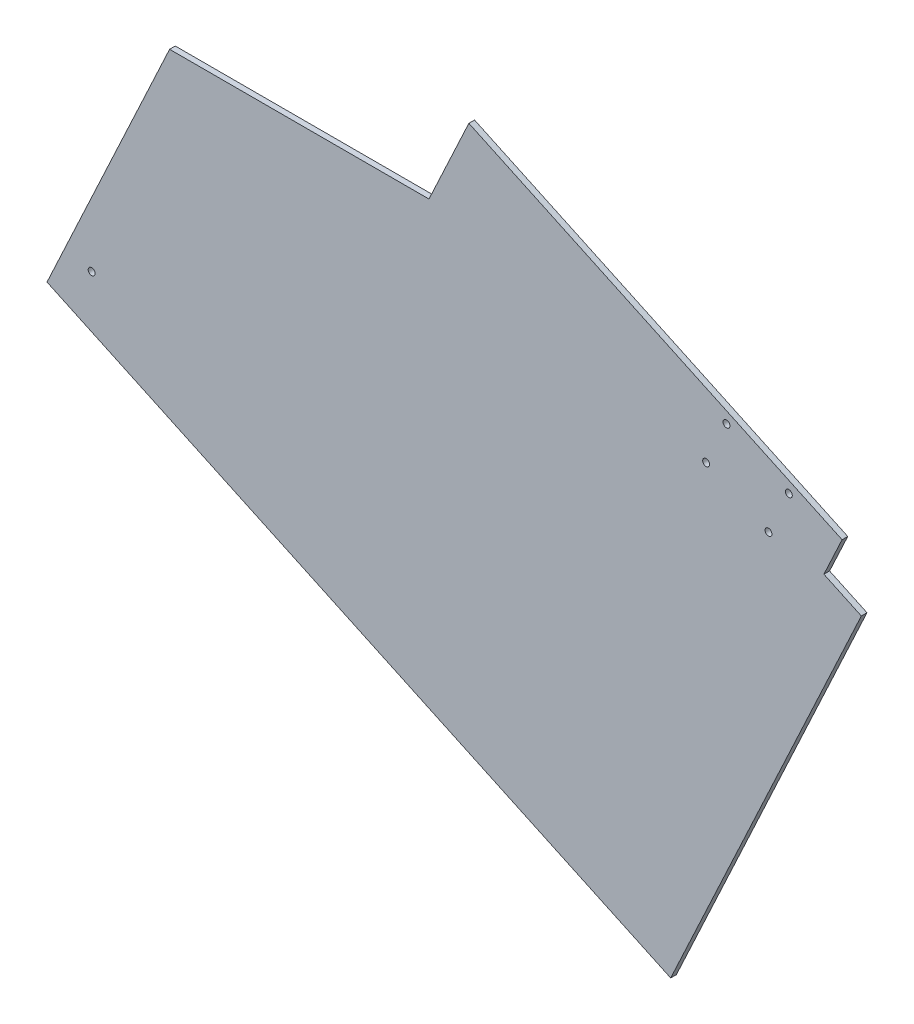
SolidWorks part; units mm, degrees
ref_plane "Front Plane" through (0, 0, 0) normal (0, 0, 1) x (1, 0, 0)
ref_plane "Top Plane" through (0, 0, 0) normal (0, 1, 0) x (1, 0, 0)
ref_plane "Right Plane" through (0, 0, 0) normal (1, 0, 0) x (0, 0, -1)
sketch "Sketch1" plane through (0, 0, 0) normal (0, 0, 1) x (1, 0, 0)
  line L0 (-261.1014, 0.0035) -> (-110.3324, 0.0035)
  line L1 (-110.3324, 0.0035) -> (-87.1479, 49.7228)
  line L2 (-87.1479, 49.7228) -> (129.7831, -51.4338)
  line L3 (129.7831, -51.4338) -> (119.2177, -74.0915)
  line L4 (119.2177, -74.0915) -> (140.969, -84.2344)
  line L5 (140.969, -84.2344) -> (30.1585, -321.8683)
  line L6 (30.1585, -321.8683) -> (-332.3646, -152.8209)
  line L7 (-332.3646, -152.8209) -> (-261.1014, 0.0035)
  line L8 (-257.4117, 0.0035) -> (-57.4117, 0.0035) construction
  line L9 (-332.3646, -152.8209) -> (-261.0998, 0.0069) construction
  line L10 (30.1585, -321.8683) -> (-332.3646, -152.8209) construction
  line L11 (140.969, -84.2344) -> (30.1585, -321.8683) construction
  line L12 (-189.2372, 97.3278) -> (129.7831, -51.4338) construction
  line L13 (119.2177, -74.0915) -> (140.969, -84.2344) construction
  line L14 (129.7831, -51.4338) -> (119.2177, -74.0915) construction
  line L15 (-110.3324, 0.0035) -> (-87.1479, 49.7228) construction
  circle A0 centre (87.0035, -69.0002) radius 2
  circle A1 centre (98.8369, -43.6236) radius 2
  circle A2 centre (62.5845, -26.7189) radius 2
  circle A3 centre (50.7512, -52.0955) radius 2
  circle A5 centre (-306.4229, -134.5749) radius 2
  dimension "D1" = 4
  dimension "D2" = 4
  dimension "D3" = 4
  dimension "D4" = 4
  dimension "D7" = 4
  dimension "D5" = 27.5
  dimension "D6" = 15.8
extrude "Boss-Extrude1" add sketch "Sketch1" along normal up to surface (3.3 mm away)
